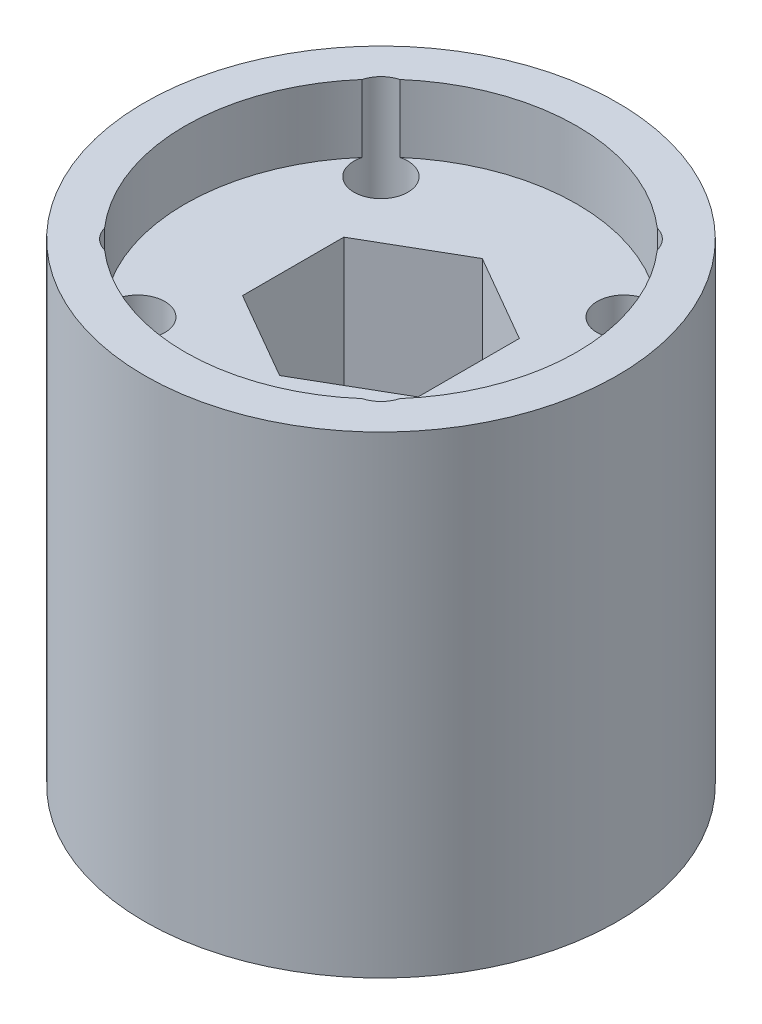
SolidWorks part; units mm, degrees
ref_plane "Спереди" through (0, 0, 0) normal (0, 0, 1) x (1, 0, 0)
ref_plane "Сверху" through (0, 0, 0) normal (0, 1, 0) x (1, 0, 0)
ref_plane "Справа" through (0, 0, 0) normal (1, 0, 0) x (0, 0, -1)
sketch "Sketch1" plane through (0, 0, 0) normal (0, 1, 0) x (1, 0, 0)
  line L1 (12.3744, -12.3744) -> (-12.3744, -12.3744) construction
  line L2 (12.3744, -12.3744) -> (12.3744, 12.3744) construction
  line L3 (12.3744, 12.3744) -> (-12.3744, 12.3744) construction
  line L4 (-12.3744, -12.3744) -> (-12.3744, 12.3744) construction
  line L5 (12.3744, -12.3744) -> (-12.3744, 12.3744) construction
  line L6 (12.3744, 12.3744) -> (-12.3744, -12.3744) construction
  circle A0 centre (0, 0) radius 17.5
  point P0 (0, 0)
  dimension "D1" = 35
extrude "Boss-Extrude1" add sketch "Sketch1" along normal blind 35
sketch "Sketch2" plane through (0, 35, 0) normal (0, 1, 0) x (1, 0, 0)
  line L1 (0, 7.5) -> (-6.4952, 3.75)
  line L2 (-6.4952, 3.75) -> (-6.4952, -3.75)
  line L3 (-6.4952, -3.75) -> (0, -7.5)
  line L4 (0, -7.5) -> (6.4952, -3.75)
  line L5 (6.4952, -3.75) -> (6.4952, 3.75)
  line L6 (6.4952, 3.75) -> (0, 7.5)
  circle A0 centre (0, 0) radius 7.5 construction
  dimension "D1" = 15
extrude "Cut-Extrude1" cut sketch "Sketch2" against normal blind 15
sketch "Sketch3" plane through (0, 20, 0) normal (0, 1, 0) x (1, 0, 0)
  circle A0 centre (0, 0) radius 4.1
  dimension "D1" = 8.2
extrude "Cut-Extrude2" cut sketch "Sketch3" against normal through all
sketch "Sketch4" plane through (0, 35, 0) normal (0, 1, 0) x (1, 0, 0)
  line L1 (9, -9) -> (-9, -9) construction
  line L2 (9, -9) -> (9, 9) construction
  line L3 (9, 9) -> (-9, 9) construction
  line L4 (-9, -9) -> (-9, 9) construction
  line L5 (9, -9) -> (-9, 9) construction
  line L6 (9, 9) -> (-9, -9) construction
  circle A0 centre (-9, 9) radius 2
  circle A1 centre (9, 9) radius 2
  circle A2 centre (9, -9) radius 2
  circle A3 centre (-9, -9) radius 2
  point P0 (0, 0)
  dimension "D1" = 4
  dimension "D2" = 18
extrude "Cut-Extrude3" cut sketch "Sketch4" against normal through all
sketch "Sketch5" plane through (0, 35, 0) normal (0, 1, 0) x (1, 0, 0)
  circle A0 centre (0, 0) radius 14.5
  circle A1 centre (0, 0) radius 17.5 construction
  dimension "D1" = 3
extrude "Cut-Extrude4" cut sketch "Sketch5" against normal blind 5
